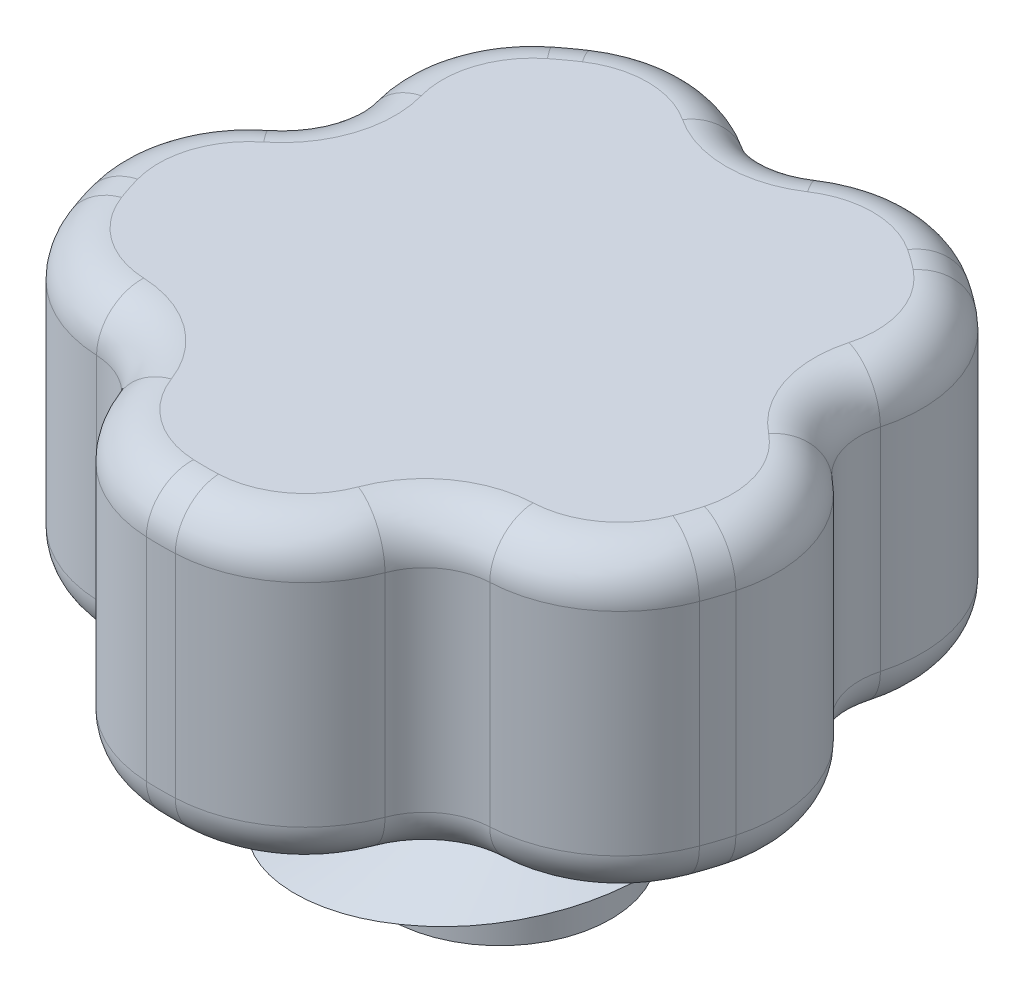
SolidWorks part; units mm, degrees
ref_plane "Front Plane" through (0, 0, 0) normal (0, 0, 1) x (1, 0, 0)
ref_plane "Top Plane" through (0, 0, 0) normal (0, 1, 0) x (1, 0, 0)
ref_plane "Right Plane" through (0, 0, 0) normal (1, 0, 0) x (0, 0, -1)
sketch "Sketch1" plane through (0, 0, 0) normal (0, 1, 0) x (1, 0, 0)
  circle A0 centre (0, 0) radius 7.5
  dimension "D1" = 15
extrude "Boss-Extrude1" add sketch "Sketch1" along normal blind 6.68
sketch "Sketch2" plane through (0, 0, 0) normal (0, -1, 0) x (1, 0, 0)
  circle A0 centre (0, 0) radius 2.45
  dimension "D1" = 4.9
extrude "Boss-Extrude2" add sketch "Sketch2" along normal blind 4
sketch "Sketch3" plane through (0, -4, 0) normal (0, -1, 0) x (1, 0, 0)
  circle A1 centre (0, 0) radius 2.45
  circle A2 centre (0, 0) radius 2.45
  dimension "D1" = 0
curve "Helix/Spiral1" pitch 4 height 4 turns 1
sketch "Sketch4" plane through (0, 0, 0) normal (0, 0, 1) x (1, 0, 0)
  line L0 (-2.45, -4) -> (-2.45, -4.75)
  line L1 (-2.45, -4.75) -> (-3.95, -4)
  line L2 (-3.95, -4) -> (-2.45, -3.25)
  line L3 (-2.45, 0) -> (-2.45, -4) construction
  line L4 (-2.45, -3.25) -> (-2.45, -4)
  point P4 (0, 0)
  dimension "D1" = 0.75
  dimension "D2" = 1.5
sweep "Sweep1" add profiles "Sketch4" path "Helix/Spiral1"
sketch "Sketch5" plane through (0, -4, 0) normal (0, -1, 0) x (1, 0, 0)
  arc A1 (-2.45, 0) -> (-0.9314, 2.266) centre (0, 0) ccw
  arc A2 (-2.45, 0) -> (-0.9314, 2.266) centre (0, 0) ccw
  spline S1 degree 3 poles (-975.931, 2839.2137) (4.1975, 1.0208) (0.6798, 3.4141) (-1.7794, 1.7775) (-2.2294, 1.0958) (-5.0015, -7.6945) (52.467, -25.9128) (-2967.6943, 454.1608) knots -2.317884 -2.317884 -2.317884 -2.317884 0.002403 0.33439 0.666376 0.833095 9.856213 9.856213 9.856213 9.856213 only from (-0.9314, 2.266) to (-2.45, 0)
  spline S2 degree 3 poles (-0.9314, 2.266) (-0.9336, 2.2652) (-1.2303, 2.1429) (-1.7794, 1.7775) (-2.2294, 1.0958) (-2.4232, 0.4813) (-2.4411, 0.1605) (-2.45, 0) knots 0 0 0 0 0.002403 0.33439 0.666376 0.833095 1 1 1 1
  dimension "D1" = 0
sketch "Sketch6" plane through (0, 6.68, 0) normal (0, 1, 0) x (1, 0, 0)
  circle A0 centre (0, 7.5) radius 1.5
  circle A1 centre (0, 0) radius 7.5 construction
  circle A2 centre (7.1329, 2.3176) radius 1.5
  circle A3 centre (4.4084, -6.0676) radius 1.5
  circle A4 centre (-4.4084, -6.0676) radius 1.5
  circle A5 centre (-7.1329, 2.3176) radius 1.5
  point P14 (0, 0)
  dimension "D1" = 3
  dimension "D2" = 5
extrude "Cut-Extrude1" cut sketch "Sketch6" against normal blind 17.75
fillet "Fillet2" radius 3 10 edges at (-3.1128, 3.34, 6.8235) (-5.5277, 3.34, 5.069) (5.5277, 3.34, 5.069) (3.1128, 3.34, 6.8235) (6.5291, 3.34, -3.6907) (7.4515, 3.34, -0.8518) (-1.4925, 3.34, -7.35) (1.4925, 3.34, -7.35) (-7.4515, 3.34, -0.8518) (-6.5291, 3.34, -3.6907)
fillet "Fillet3" radius 1 20 edges at (-7.1883, 6.68, 0.2799) (-5.7063, 6.68, -1.8541) (-5.651, 6.68, -4.4516) (-4.4084, 6.68, -6.0676) (-2.4875, 6.68, -6.75) (0, 6.68, -6) (2.4875, 6.68, -6.75) (4.4084, 6.68, -6.0676) (5.651, 6.68, -4.4516) (5.7063, 6.68, -1.8541) (7.1883, 6.68, 0.2799) (7.1329, 6.68, 2.3176) (5.98, 6.68, 3.9988) (3.5267, 6.68, 4.8541) (1.9551, 6.68, 6.923) (0, 6.68, 7.5) (-1.9551, 6.68, 6.923) (-3.5267, 6.68, 4.8541) (-5.98, 6.68, 3.9988) (-7.1329, 6.68, 2.3176)
fillet "Fillet4" radius 1 20 edges at (-3.5267, 0, 4.8541) (-1.9551, 0, 6.923) (0, 0, 7.5) (1.9551, 0, 6.923) (3.5267, 0, 4.8541) (5.98, 0, 3.9988) (7.1329, 0, 2.3176) (7.1883, 0, 0.2799) (5.7063, 0, -1.8541) (5.651, 0, -4.4516) (4.4084, 0, -6.0676) (2.4875, 0, -6.75) (0, 0, -6) (-2.4875, 0, -6.75) (-4.4084, 0, -6.0676) (-5.651, 0, -4.4516) (-5.7063, 0, -1.8541) (-7.1883, 0, 0.2799) (-7.1329, 0, 2.3176) (-5.98, 0, 3.9988)
